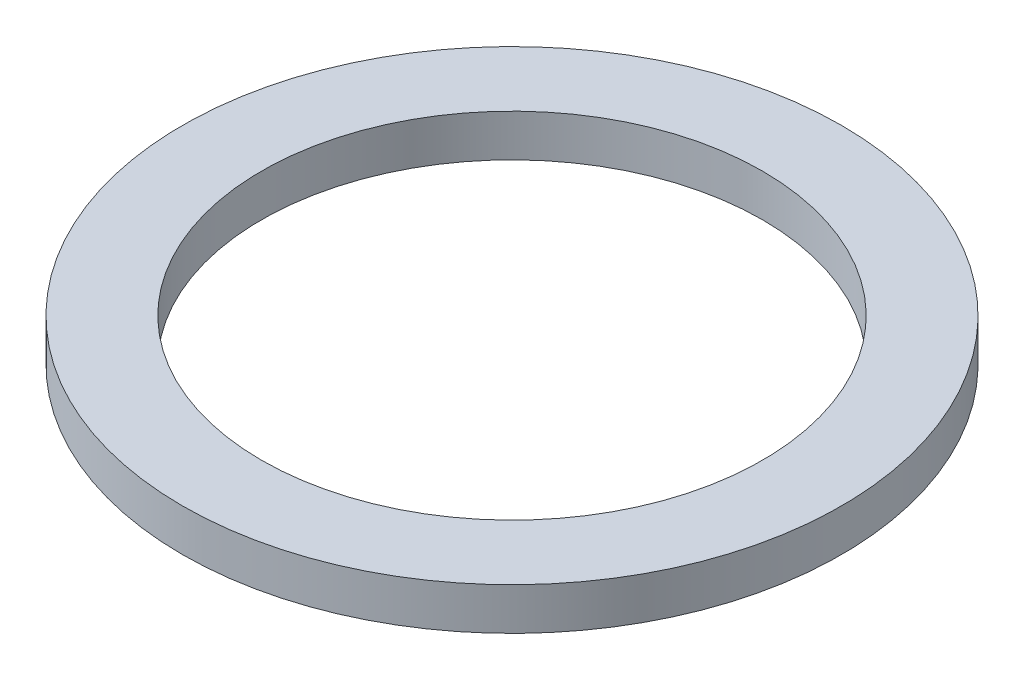
SolidWorks part; units mm, degrees
ref_plane "Front Plane" through (0, 0, 0) normal (0, 0, 1) x (1, 0, 0)
ref_plane "Top Plane" through (0, 0, 0) normal (0, 1, 0) x (1, 0, 0)
ref_plane "Right Plane" through (0, 0, 0) normal (1, 0, 0) x (0, 0, -1)
sketch "Sketch1" plane through (0, 0, 0) normal (0, 1, 0) x (1, 0, 0)
  circle A0 centre (0, 0) radius 62.5
  dimension "FLANGE_OD" = 125
extrude "Boss-Extrude1" add sketch "Sketch1" along normal blind 8
sketch "Sketch2" plane through (0, 0, 0) normal (0, 1, 0) x (1, 0, 0)
  circle A0 centre (0, 0) radius 47.5
  dimension "BORE_D" = 95
extrude "Cut-Extrude1" cut sketch "Sketch2" along normal through all
sketch "Sketch3" plane through (0, 8, 0) normal (0, 1, 0) x (1, 0, 0)
  circle A0 centre (0, 0) radius 27.2735 construction
  circle A1 centre (-27.2735, 0) radius 1.9097
  dimension "BOLT_D" = 3.8194
  dimension "BOLT_PCD" = 54.5471
extrude "Cut-Extrude2" cut sketch "Sketch3" against normal blind 6.2875 rebuild error yes
pattern_circular "CirPattern1" count 5 over 360 rebuild error yes
